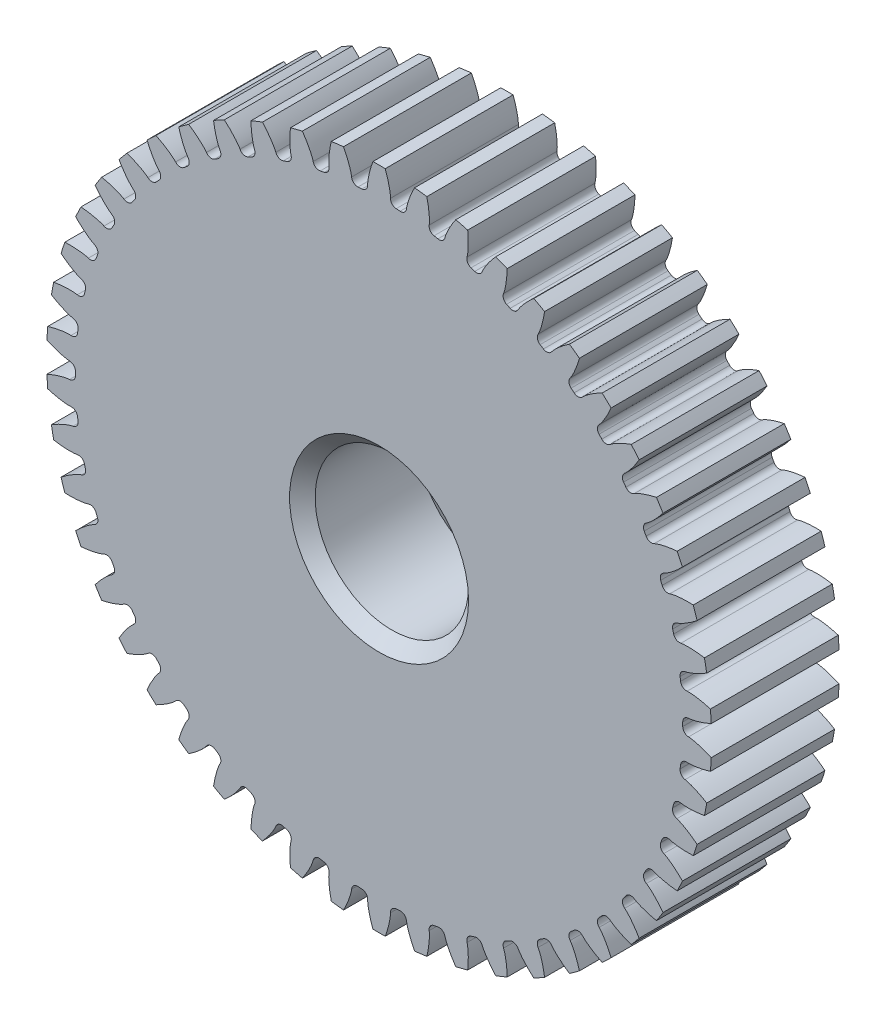
SolidWorks part; units mm, degrees
ref_plane "Front Plane" through (0, 0, 0) normal (0, 0, 1) x (1, 0, 0)
ref_plane "Top Plane" through (0, 0, 0) normal (0, 1, 0) x (1, 0, 0)
ref_plane "Right Plane" through (0, 0, 0) normal (1, 0, 0) x (0, 0, -1)
sketch "Sketch1" plane through (0, 0, 0) normal (0, 0, 1) x (1, 0, 0)
  circle A0 centre (0, 0) radius 16.51
extrude "BodyBlank" add sketch "Sketch1" along normal blind 6.35
ref_plane "CirclesPlane" through (0, 0, 6.35) normal (0, 0, 1) x (1, 0, 0)
sketch "EqDrivenInvoluteCurves" plane through (0, 0, 6.35) normal (0, 0, 1) x (1, 0, 0)
  line L0 (0, 0) -> (15.0762, 0.3901) construction
  line L1 (15.0762, -0.3901) -> (0, 0) construction
  line L2 (15.3709, 0.3978) -> (15.3642, 0.3976)
  line L3 (15.3709, -0.3978) -> (15.3642, -0.3976)
  circle A0 centre (0, 0) radius 15.0813 construction
  circle A1 centre (0, 0) radius 15.3693 construction
  circle A2 centre (0, 0) radius 15.875 construction
  circle A3 centre (0, 0) radius 16.51 construction
  arc A4 (16.4938, 0.7316) -> (16.4938, -0.7316) centre (0, 0) cw
  arc A5 (15.0809, 0.0983) -> (15.0809, -0.0983) centre (0, 0) cw
  arc A6 (15.3709, 0.3978) -> (15.0809, 0.0983) centre (15.3786, 0.1002) ccw
  arc A7 (15.0809, -0.0983) -> (15.3709, -0.3978) centre (15.3786, -0.1002) ccw
  spline S0 degree 4 poles (15.3642, 0.3976) (15.3659, 0.3976) (15.3709, 0.3978) (15.3801, 0.3984) (15.3952, 0.3996) (15.4145, 0.4015) (15.4394, 0.4044) (15.4687, 0.4083) (15.5009, 0.4133) (15.536, 0.4192) (15.571, 0.4257) (15.606, 0.4327) (15.6408, 0.4402) (15.6829, 0.4497) (15.7335, 0.462) (15.7927, 0.4774) (15.8598, 0.4962) (15.9283, 0.5168) (15.9958, 0.5383) (16.064, 0.5613) (16.13, 0.5845) (16.1987, 0.61) (16.2621, 0.6343) (16.3332, 0.663) (16.3906, 0.6866) (16.4665, 0.7194) (16.5113, 0.7393) (16.5639, 0.7632) (16.5872, 0.7741) (16.6016, 0.7808) knots 0 0 0 0 0 0.005377 0.015084 0.028532 0.04661 0.064855 0.092111 0.119476 0.146842 0.174209 0.201575 0.228941 0.256307 0.307035 0.361767 0.4165 0.471232 0.525964 0.580697 0.635429 0.690161 0.744894 0.799626 0.854358 0.909091 0.954545 1 1 1 1 1 construction
  spline S1 degree 4 poles (15.3642, 0.3976) (15.3659, 0.3976) (15.3709, 0.3978) (15.3801, 0.3984) (15.3952, 0.3996) (15.4145, 0.4015) (15.4394, 0.4044) (15.4687, 0.4083) (15.5009, 0.4133) (15.536, 0.4192) (15.571, 0.4257) (15.606, 0.4327) (15.6408, 0.4402) (15.6829, 0.4497) (15.7335, 0.462) (15.7927, 0.4774) (15.8598, 0.4962) (15.9283, 0.5168) (15.9958, 0.5383) (16.064, 0.5613) (16.13, 0.5845) (16.1987, 0.61) (16.2621, 0.6343) (16.3332, 0.663) (16.3906, 0.6866) (16.4501, 0.7123) (16.479, 0.725) (16.4938, 0.7316) knots 0 0 0 0 0 0.005377 0.015084 0.028532 0.04661 0.064855 0.092111 0.119476 0.146842 0.174209 0.201575 0.228941 0.256307 0.307035 0.361767 0.4165 0.471232 0.525964 0.580697 0.635429 0.690161 0.744894 0.799626 0.854358 0.909091 0.909091 0.909091 0.909091 0.909091
  spline S2 degree 4 poles (15.3642, -0.3976) (15.3659, -0.3976) (15.3709, -0.3978) (15.3801, -0.3984) (15.3952, -0.3996) (15.4145, -0.4015) (15.4394, -0.4044) (15.4687, -0.4083) (15.5009, -0.4133) (15.536, -0.4192) (15.571, -0.4257) (15.606, -0.4327) (15.6408, -0.4402) (15.6829, -0.4497) (15.7335, -0.462) (15.7927, -0.4774) (15.8598, -0.4962) (15.9283, -0.5168) (15.9958, -0.5383) (16.064, -0.5613) (16.13, -0.5845) (16.1987, -0.61) (16.2621, -0.6343) (16.3332, -0.663) (16.3906, -0.6866) (16.4665, -0.7194) (16.5113, -0.7393) (16.5639, -0.7632) (16.5872, -0.7741) (16.6016, -0.7808) knots 0 0 0 0 0 0.005377 0.015084 0.028532 0.04661 0.064855 0.092111 0.119476 0.146842 0.174209 0.201575 0.228941 0.256307 0.307035 0.361767 0.4165 0.471232 0.525964 0.580697 0.635429 0.690161 0.744894 0.799626 0.854358 0.909091 0.954545 1 1 1 1 1 construction
  spline S3 degree 4 poles (15.3642, -0.3976) (15.3659, -0.3976) (15.3709, -0.3978) (15.3801, -0.3984) (15.3952, -0.3996) (15.4145, -0.4015) (15.4394, -0.4044) (15.4687, -0.4083) (15.5009, -0.4133) (15.536, -0.4192) (15.571, -0.4257) (15.606, -0.4327) (15.6408, -0.4402) (15.6829, -0.4497) (15.7335, -0.462) (15.7927, -0.4774) (15.8598, -0.4962) (15.9283, -0.5168) (15.9958, -0.5383) (16.064, -0.5613) (16.13, -0.5845) (16.1987, -0.61) (16.2621, -0.6343) (16.3332, -0.663) (16.3906, -0.6866) (16.4501, -0.7123) (16.479, -0.725) (16.4938, -0.7316) knots 0 0 0 0 0 0.005377 0.015084 0.028532 0.04661 0.064855 0.092111 0.119476 0.146842 0.174209 0.201575 0.228941 0.256307 0.307035 0.361767 0.4165 0.471232 0.525964 0.580697 0.635429 0.690161 0.744894 0.799626 0.854358 0.909091 0.909091 0.909091 0.909091 0.909091
  dimension "D5" = 0.2977
extrude "ToothCutMaster" cut sketch "EqDrivenInvoluteCurves" against normal through all
pattern_circular "ToothCutsPattern" count 50 over 360 about axis through (0, 0, 6.35) along (0, 0, -1) of "ToothCutMaster"
sketch "Sketch2" plane through (0, 0, 6.35) normal (0, 0, 1) x (1, 0, 0)
  circle A0 centre (0, 0) radius 3.81
  dimension "D1" = 7.62
extrude "Cut-Extrude1" cut sketch "Sketch2" against normal through all
chamfer "Chamfer1" distance 0.635 angle 45 2 edges at (3.81, 0, 0) (3.81, 0, 6.35)
equation "\"DiametralPitch\"= 40"
equation "\"NumTeeth\"= 50"
equation "\"FaceWidth\"=0.25"
equation "\"PressureAngle\"= 14.5deg'Default: 14.5"
equation "\"Addendum\"= 1 / \"DiametralPitch\""
equation "\"Dedendum\"= 1.25 / \"DiametralPitch\""
equation "\"WorkingDepth\"= 2 / \"DiametralPitch\""
equation "\"WholeDepth\"= 2.25 / \"DiametralPitch\""
equation "\"Clearance\"= 0.25 / \"DiametralPitch\""
equation "\"ToothThickness\"= 1.5708 / \"DiametralPitch\""
equation "\"CircularPitch\"= pi / \"DiametralPitch\""
equation "\"PitchCircle\"= \"NumTeeth\" / \"DiametralPitch\""
equation "\"OutsideDiameter\"= ( \"NumTeeth\" + 2 ) / \"DiametralPitch\""
equation "\"Fillet\"= \"Clearance\" * cos ( \"PressureAngle\" ) * tan ( ( 90 + \"PressureAngle\" ) / 2 )"
equation "\"AddendumCircle\"= \"PitchCircle\" + ( 2 * \"Addendum\" )"
equation "\"DedendumCircle\"= \"PitchCircle\" - ( 2 * \"Dedendum\" )"
equation "\"BaseCircle\"= \"PitchCircle\" * cos ( \"PressureAngle\" )"
equation "\"PitchAngle\"= 360deg / \"NumTeeth\""
equation "\"Alpha\"= sqr ( \"PitchCircle\" ^ 2 - \"BaseCircle\" ^ 2 ) / \"BaseCircle\" * 180 / PI - \"PressureAngle\""
equation "\"Beta\"= ( \"PitchAngle\" / 4 - \"Alpha\" )"
equation "\"Phi\"= sqr ( ( \"AddendumCircle\" / 2 ) ^ 2 - ( \"BaseCircle\" / 2 ) ^ 2 ) / ( \"BaseCircle\" / 2 )"
equation "\"D1@Sketch1\"=\"OutsideDiameter\""
equation "\"D1@BodyBlank\" = \"FaceWidth\""
equation "\"D1@EqDrivenInvoluteCurves\" = \"OutsideDiameter\""
equation "\"D2@EqDrivenInvoluteCurves\" = \"PitchCircle\""
equation "\"D3@EqDrivenInvoluteCurves\" = \"BaseCircle\""
equation "\"D4@EqDrivenInvoluteCurves\" = \"DedendumCircle\""
equation "\"D1@ToothCutsPattern\"=\"NumTeeth\""
